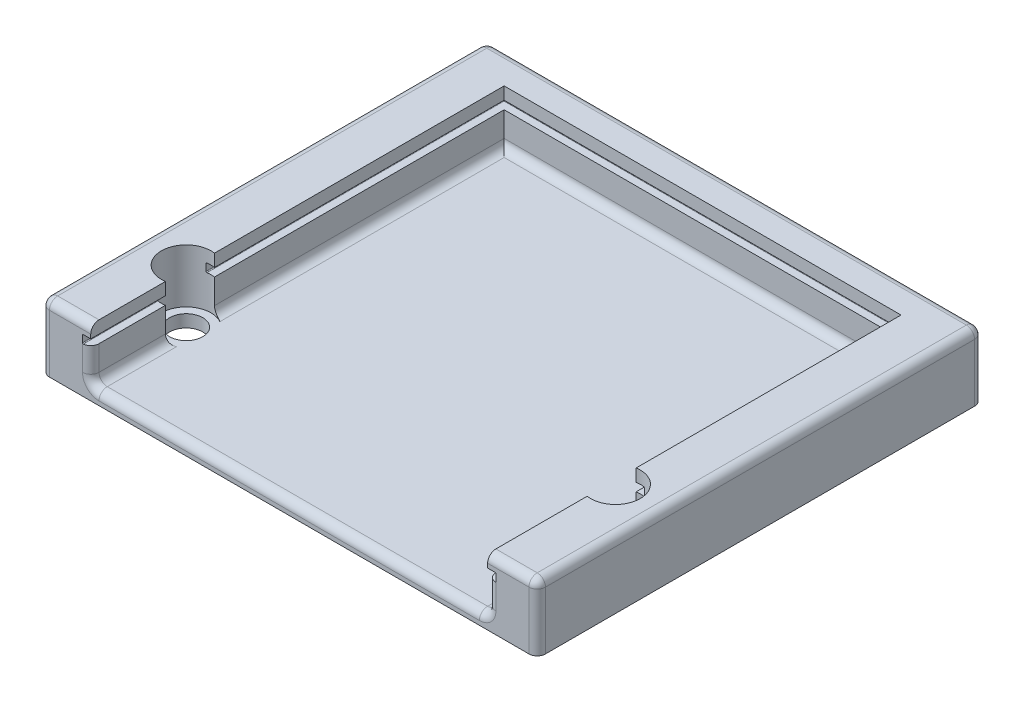
SolidWorks part; units mm, degrees
note: The reader was unsure of these and kept them because the rebuilt part matched: shared geometry of "Sketch2<7>".
ref_plane "Front Plane" through (0, 0, 0) normal (0, 0, 1) x (1, 0, 0)
ref_plane "Top Plane" through (0, 0, 0) normal (0, 1, 0) x (1, 0, 0)
ref_plane "Right Plane" through (0, 0, 0) normal (1, 0, 0) x (0, 0, -1)
sketch "Sketch2" plane through (0, 0, 0) normal (0, 1, 0) x (1, 0, 0)
  line L1 (0, 0) -> (60, 0)
  line L2 (0, 0) -> (0, 50)
  line L3 (0, 50) -> (60, 50)
  line L4 (60, 0) -> (60, 50)
  line L12 (6, 50) -> (6, 0)
  line L13 (54, 50) -> (54, 0)
  line L14 (0, 0) -> (-2, 0)
  line L15 (0, 25) -> (6, 25) construction
  line L16 (-2, 0) -> (-4, 0)
  line L17 (54, 25) -> (60, 25) construction
  line L18 (60, 0) -> (59, 0)
  line L19 (59, 0) -> (61, 0)
  line L20 (0, 50) -> (0, 53.897)
  line L21 (0, 53.897) -> (60, 53.897)
  line L22 (60, 50) -> (60, 53.897)
  line L23 (54.454, 15) -> (60, 15) construction
  line L24 (5.546, 12) -> (0, 12) construction
  circle A0 centre (5.546, 12) radius 2
  circle A1 centre (54.454, 15) radius 2
  circle A2 centre (5.546, 12) radius 3
  circle A3 centre (54.454, 15) radius 3
  dimension "D3" = 12
  dimension "D8" = 1
  dimension "D1" = 48
  dimension "D2" = 50
  dimension "D4" = 15
  dimension "D5" = 49
  dimension "D7" = 1
  dimension "D9" = 60
extrude "Boss-Extrude1" add sketch "Sketch2" along normal blind 1.5 contours A3 L13 L3 L12 A2 L1 | L13 A3 A1 | L13 A3 A1 | L12 A2 A0 | L12 A2 A0
extrude "Boss-Extrude4" add sketch "Sketch2<7>" along normal blind 8 contours A0 L12 L3 L2 L1 | L3 L22 L21 L20 | A3 L13 L1 L4 L3
sketch "Sketch2<7>" plane through (0, 0, 0) normal (0, 1, 0) x (1, 0, 0) same geometry as "Sketch2"
sketch "Sketch3" plane through (0, 8, 0) normal (0, 1, 0) x (1, 0, 0)
  line L0 (5, 0) -> (5, 51)
  line L1 (54, 33.9827) -> (55, 33.9827) construction
  line L2 (0, 0) -> (6, 0) construction
  line L3 (5, 51) -> (55, 51)
  line L4 (55, 51) -> (55, 0)
  line L5 (54, 0) -> (60, 0) construction
  line L6 (5, 25.5) -> (6, 25.5) construction
  line L7 (6, 50) -> (6, 14.9654) construction
  line L8 (54, 50) -> (54, 17.9654) construction
  line L10 (30, 51) -> (30, 50) construction
  line L11 (6, 50) -> (54, 50) construction
  dimension "D1" = 50
sketch "Sketch6" plane through (6, 0, 0) normal (1, 0, 0) x (0, 0, -1)
  line L0 (0, 5.5) -> (50, 5.5)
  line L1 (0, 8) -> (0, 1.5) construction
  line L2 (50, 8) -> (50, 1.5) construction
  line L3 (0, 6.5) -> (50, 6.5)
  line L4 (0, 6.5) -> (0, 5.5)
  line L5 (50, 6.5) -> (50, 5.5)
  line L8 (9.0346, 1.5) -> (0, 1.5) construction
  dimension "D1" = 1
  dimension "D2" = 4
extrude "Cut-Extrude1" cut sketch "Sketch6" against normal blind 1
sketch "Sketch10" plane through (54, 0, 0) normal (-1, 0, 0) x (0, 0, 1)
  line L0 (-50, 8) -> (-50, 1.5) construction
  line L1 (-50, 5.5) -> (0, 5.5)
  line L2 (-50, 5.5) -> (-50, 6.5)
  line L3 (-50, 6.5) -> (0, 6.5)
  line L4 (0, 5.5) -> (0, 6.5)
  line L5 (0, 8) -> (0, 1.5) construction
  line L7 (-12.0346, 1.5) -> (0, 1.5) construction
  dimension "D1" = 1
  dimension "D2" = 4
extrude "Cut-Extrude2" cut sketch "Sketch10" against normal blind 1
sketch "Sketch11" plane through (0, 0, -50) normal (0, 0, 1) x (1, 0, 0)
  line L1 (5, 5.5) -> (55, 5.5)
  line L2 (5, 5.5) -> (5, 6.5)
  line L3 (5, 6.5) -> (55, 6.5)
  line L4 (55, 5.5) -> (55, 6.5)
extrude "Cut-Extrude3" cut sketch "Sketch11" against normal blind 1
fillet "Fillet1" radius 1 17 edges at (6, 1.5, -4.5173) (6, 1.5, -32.4827) (30, 1.5, -50) (54, 1.5, -33.9827) (54, 1.5, -6.0173) (30, 1.5, 0) (54, 3.5, 0) (6, 3.5, 0) (60, 4, -53.897) (0, 4, -53.897) (30, 8, -53.897) (0, 4, 0) (60, 4, 0) (60, 8, -26.9485) (57, 8, 0) (3, 8, 0) (0, 8, -26.9485)
fillet "Fillet2" radius 0.1 8 edges at (5, 6.5, -4.525) (5, 5.5, -4.525) (5, 5.5, -32.975) (5, 6.5, -32.975) (30, 6.5, -51) (30, 5.5, -51) (55, 5.5, -6.025) (55, 6.5, -6.025)
